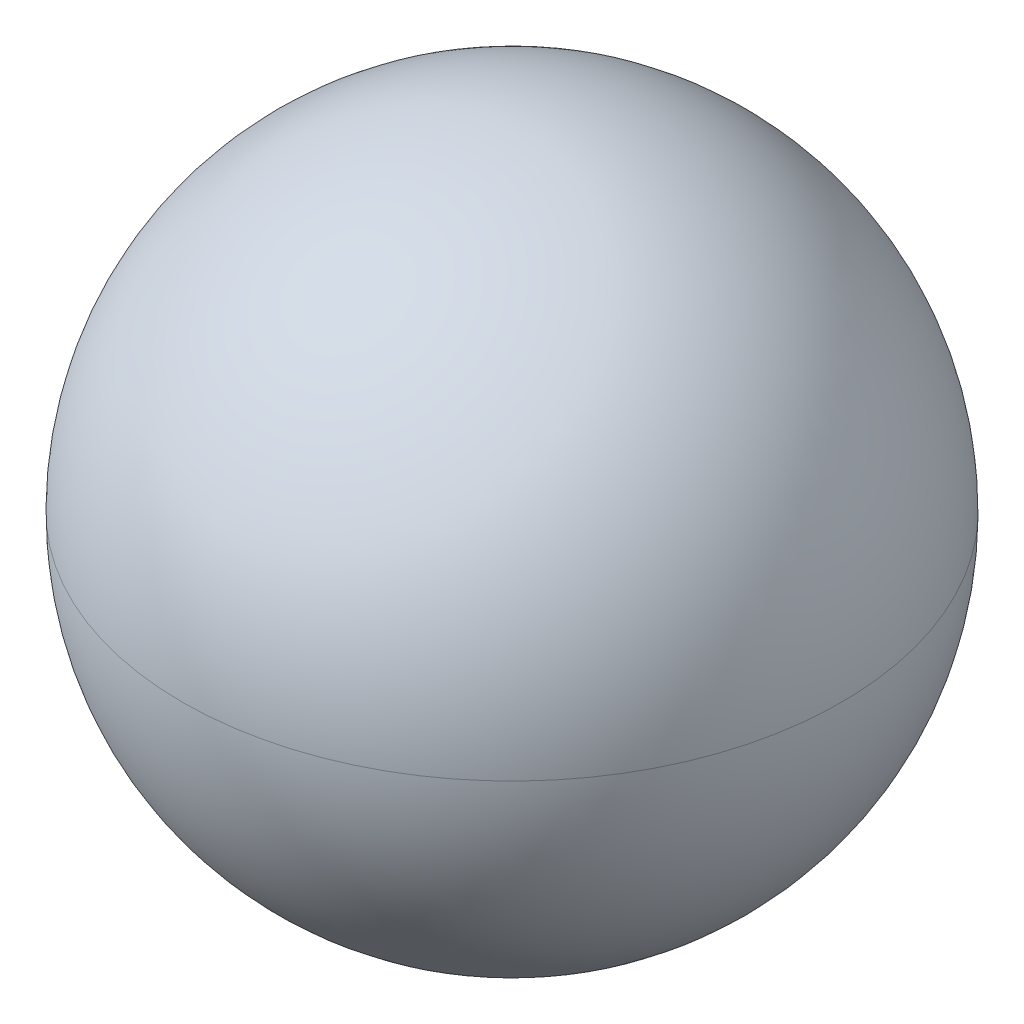
SolidWorks part; units mm, degrees
ref_plane "Front Plane" through (0, 0, 0) normal (0, 0, 1) x (1, 0, 0)
ref_plane "Top Plane" through (0, 0, 0) normal (0, 1, 0) x (1, 0, 0)
ref_plane "Right Plane" through (0, 0, 0) normal (1, 0, 0) x (0, 0, -1)
sketch "Sketch1" plane through (0, 0, 0) normal (0, 1, 0) x (1, 0, 0)
  circle A0 centre (0, 0) radius 381
  dimension "D1" = 762
extrude "Boss-Extrude1" add sketch "Sketch1" along normal blind 762
fillet "Fillet1" radius 381 2 edges at (0, 0, 381) (0, 762, 381)
